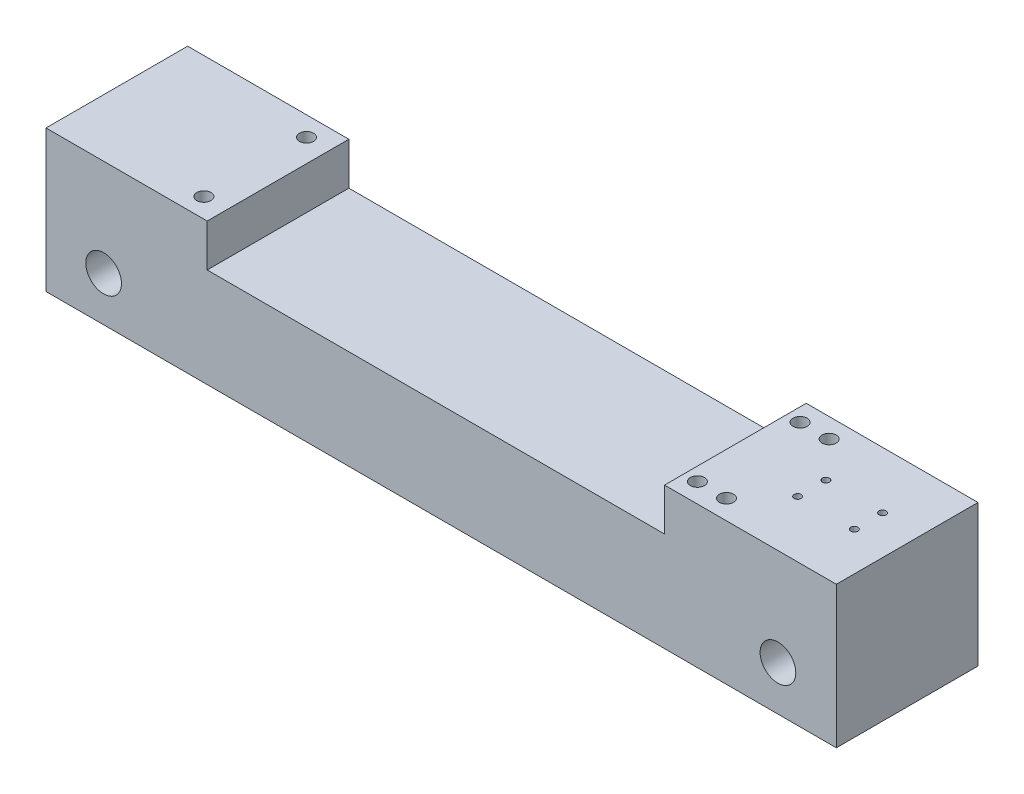
SolidWorks part; units mm, degrees
material "6061 Alloy"
ref_plane "Front Plane" through (0, 0, 0) normal (0, 0, 1) x (1, 0, 0)
ref_plane "Top Plane" through (0, 0, 0) normal (0, 1, 0) x (1, 0, 0)
ref_plane "Right Plane" through (0, 0, 0) normal (1, 0, 0) x (0, 0, -1)
sketch "Sketch1" plane through (0, 0, 0) normal (0, 0, 1) x (1, 0, 0)
  line L0 (177.125, 59) -> (177.125, 63.5)
  line L1 (177.125, 63.5) -> (100.125, 63.5)
  line L2 (100.125, 63.5) -> (100.125, 59)
  line L3 (100.125, 44.5) -> (-104.875, 44.5)
  line L4 (-2.375, 44.5) -> (-2.375, 40)
  line L5 (-104.875, 63.5) -> (-177.125, 63.5)
  line L6 (-177.125, 63.5) -> (-177.125, 59)
  line L7 (-104.875, 63.5) -> (-104.875, 59)
  circle A0 centre (164.385, 33.435) radius 2.6035
  circle A1 centre (169.95, 20) radius 2.6035
  circle A2 centre (164.385, 6.565) radius 2.6035
  circle A3 centre (137.515, 6.565) radius 2.6035
  circle A4 centre (131.95, 20) radius 2.6035
  circle A5 centre (137.515, 33.435) radius 2.6035
  circle A6 centre (-137.865, 33.435) radius 2.6035
  circle A7 centre (-132.3, 20) radius 2.6035
  circle A8 centre (-137.865, 6.565) radius 2.6035
  circle A9 centre (-164.735, 6.565) radius 2.6035
  circle A10 centre (-170.3, 20) radius 2.6035
  circle A11 centre (-164.735, 33.435) radius 2.6035
  point P37 (-182.0987, 63.5)
  line B0 (-177.125, 0) -> (177.125, 0)
  line B1 (177.125, 0) -> (177.125, 59)
  line B2 (177.125, 59) -> (100.125, 59)
  line B3 (100.125, 59) -> (100.125, 40)
  line B4 (100.125, 40) -> (-104.875, 40)
  line B5 (-104.875, 40) -> (-104.875, 59)
  line B6 (-104.875, 59) -> (-177.125, 59)
  line B7 (-177.125, 59) -> (-177.125, 0)
  circle B8 centre (-151.3, 20) radius 14
  circle B9 centre (150.95, 20) radius 14
  arc B10 (-164.735, 9.315) -> (-164.735, 3.815) centre (-164.735, 6.565) ccw
  arc B11 (-164.735, 9.315) -> (-164.735, 3.815) centre (-164.735, 6.565) ccw
  arc B12 (-164.735, 3.815) -> (-164.735, 9.315) centre (-164.735, 6.565) ccw
  arc B13 (-164.735, 3.815) -> (-164.735, 9.315) centre (-164.735, 6.565) ccw
  arc B14 (-137.865, 3.815) -> (-137.865, 9.315) centre (-137.865, 6.565) ccw
  arc B15 (-137.865, 3.815) -> (-137.865, 9.315) centre (-137.865, 6.565) ccw
  arc B16 (-137.865, 9.315) -> (-137.865, 3.815) centre (-137.865, 6.565) ccw
  arc B17 (-137.865, 9.315) -> (-137.865, 3.815) centre (-137.865, 6.565) ccw
  arc B18 (-132.3, 17.25) -> (-132.3, 22.75) centre (-132.3, 20) ccw
  arc B19 (-132.3, 17.25) -> (-132.3, 22.75) centre (-132.3, 20) ccw
  arc B20 (-132.3, 22.75) -> (-132.3, 17.25) centre (-132.3, 20) ccw
  arc B21 (-132.3, 22.75) -> (-132.3, 17.25) centre (-132.3, 20) ccw
  arc B22 (-137.865, 30.685) -> (-137.865, 36.185) centre (-137.865, 33.435) ccw
  arc B23 (-137.865, 30.685) -> (-137.865, 36.185) centre (-137.865, 33.435) ccw
  arc B24 (-137.865, 36.185) -> (-137.865, 30.685) centre (-137.865, 33.435) ccw
  arc B25 (-137.865, 36.185) -> (-137.865, 30.685) centre (-137.865, 33.435) ccw
  arc B26 (-170.3, 17.25) -> (-170.3, 22.75) centre (-170.3, 20) ccw
  arc B27 (-170.3, 17.25) -> (-170.3, 22.75) centre (-170.3, 20) ccw
  arc B28 (-170.3, 22.75) -> (-170.3, 17.25) centre (-170.3, 20) ccw
  arc B29 (-170.3, 22.75) -> (-170.3, 17.25) centre (-170.3, 20) ccw
  arc B30 (-164.735, 30.685) -> (-164.735, 36.185) centre (-164.735, 33.435) ccw
  arc B31 (-164.735, 30.685) -> (-164.735, 36.185) centre (-164.735, 33.435) ccw
  arc B32 (-164.735, 36.185) -> (-164.735, 30.685) centre (-164.735, 33.435) ccw
  arc B33 (-164.735, 36.185) -> (-164.735, 30.685) centre (-164.735, 33.435) ccw
  arc B34 (137.515, 9.315) -> (137.515, 3.815) centre (137.515, 6.565) ccw
  arc B35 (137.515, 9.315) -> (137.515, 3.815) centre (137.515, 6.565) ccw
  arc B36 (137.515, 3.815) -> (137.515, 9.315) centre (137.515, 6.565) ccw
  arc B37 (137.515, 3.815) -> (137.515, 9.315) centre (137.515, 6.565) ccw
  arc B38 (164.385, 9.315) -> (164.385, 3.815) centre (164.385, 6.565) ccw
  arc B39 (164.385, 9.315) -> (164.385, 3.815) centre (164.385, 6.565) ccw
  arc B40 (164.385, 3.815) -> (164.385, 9.315) centre (164.385, 6.565) ccw
  arc B41 (164.385, 3.815) -> (164.385, 9.315) centre (164.385, 6.565) ccw
  arc B42 (169.95, 17.25) -> (169.95, 22.75) centre (169.95, 20) ccw
  arc B43 (169.95, 17.25) -> (169.95, 22.75) centre (169.95, 20) ccw
  arc B44 (169.95, 22.75) -> (169.95, 17.25) centre (169.95, 20) ccw
  arc B45 (169.95, 22.75) -> (169.95, 17.25) centre (169.95, 20) ccw
  arc B46 (164.385, 30.685) -> (164.385, 36.185) centre (164.385, 33.435) ccw
  arc B47 (164.385, 30.685) -> (164.385, 36.185) centre (164.385, 33.435) ccw
  arc B48 (164.385, 36.185) -> (164.385, 30.685) centre (164.385, 33.435) ccw
  arc B49 (164.385, 36.185) -> (164.385, 30.685) centre (164.385, 33.435) ccw
  arc B50 (131.95, 17.25) -> (131.95, 22.75) centre (131.95, 20) ccw
  arc B51 (131.95, 17.25) -> (131.95, 22.75) centre (131.95, 20) ccw
  arc B52 (131.95, 22.75) -> (131.95, 17.25) centre (131.95, 20) ccw
  arc B53 (131.95, 22.75) -> (131.95, 17.25) centre (131.95, 20) ccw
  arc B54 (137.515, 30.685) -> (137.515, 36.185) centre (137.515, 33.435) ccw
  arc B55 (137.515, 30.685) -> (137.515, 36.185) centre (137.515, 33.435) ccw
  arc B56 (137.515, 36.185) -> (137.515, 30.685) centre (137.515, 33.435) ccw
  arc B57 (137.515, 36.185) -> (137.515, 30.685) centre (137.515, 33.435) ccw
  dimension "D1" = 5.207
  dimension "D2" = 63.5
sketch_block_instance "Block-SecondaryBlock Sideview-1"
sketch_block "Block-SecondaryBlock Sideview"
extrude "Boss-Extrude1" add sketch "Sketch1" along normal blind 63.5 contours B6 B7 B0 B1 B2 B3 B4 B5 B56 B54 B52 B50 B48 B46 B44 B42 B40 B38 B36 B34 B32 B30 B28 B26 B24 B22 B20 B18 B16 B14 B12 B10 B9 B8 | B46 B48 A0 | B54 B56 A5 | B42 B44 A1 | B38 B40 A2 | B50 B52 A4 | B34 B36 A3 | B22 B24 A6 | B18 B20 A7 | B14 B16 A8 | B10 B12 A9 | B26 B28 A10 | B30 B32 A11 | B2 L0 L1 L2 | B4 B3 L3 L4 | B6 L7 L5 L6 | B5 B4 L4 L3 region at (138.625, 61.25, 0) region at (0.6144, 25.4009, 0) region at (48.875, 42.25, 0) region at (-141, 61.25, 0) region at (-53.625, 42.25, 0) region at (-162.0628, 6.565, 0) region at (-140.5372, 6.565, 0) region at (-134.9722, 20, 0) region at (-140.5372, 33.435, 0) region at (-172.9722, 20, 0) region at (-167.4072, 33.435, 0) region at (140.1872, 6.565, 0) region at (167.0572, 6.565, 0) region at (167.2778, 20, 0) region at (161.7128, 33.435, 0) region at (129.2778, 20, 0) region at (134.8428, 33.435, 0)
sketch "Sketch2" plane through (0, 63.5, 0) normal (0, 1, 0) x (1, 0, 0)
  line L0 (177.125, -61.75) -> (177.125, -1.75)
  line L2 (177.125, -63.5) -> (177.125, 0) construction
  circle A0 centre (119.125, -54.75) radius 3.175
  circle A1 centre (106.125, -54.75) radius 3.175
  circle A2 centre (119.125, -8.75) radius 3.175
  circle A3 centre (106.125, -8.75) radius 3.175
  circle A4 centre (-115.125, -54.75) radius 3.175
  circle A5 centre (-115.125, -8.75) radius 3.175
  point P13 (177.125, -31.75)
  point P20 (177.125, -31.75)
  line B0 (-177.125, -1.75) -> (177.125, -1.75)
  line B1 (177.125, -1.75) -> (177.125, -41.55)
  line B2 (177.125, -41.55) -> (-177.125, -41.55) construction
  line B3 (-177.125, -41.55) -> (-177.125, -1.75)
  line B4 (-177.125, -41.55) -> (-177.125, -61.75)
  line B5 (-177.125, -61.75) -> (177.125, -61.75)
  line B6 (177.125, -61.75) -> (177.125, -41.55)
  arc B7 (-118.425, -8.75) -> (-111.825, -8.75) centre (-115.125, -8.75) ccw
  arc B8 (-111.825, -8.75) -> (-118.425, -8.75) centre (-115.125, -8.75) ccw
  arc B9 (-118.425, -54.75) -> (-111.825, -54.75) centre (-115.125, -54.75) ccw
  arc B10 (-111.825, -54.75) -> (-118.425, -54.75) centre (-115.125, -54.75) ccw
  arc B11 (-132.725, -34.65) -> (-128.525, -34.65) centre (-130.625, -34.65) ccw
  arc B12 (-128.525, -34.65) -> (-132.725, -34.65) centre (-130.625, -34.65) ccw
  arc B13 (-132.725, -8.65) -> (-128.525, -8.65) centre (-130.625, -8.65) ccw
  arc B14 (-128.525, -8.65) -> (-132.725, -8.65) centre (-130.625, -8.65) ccw
  arc B15 (-173.725, -34.65) -> (-169.525, -34.65) centre (-171.625, -34.65) ccw
  arc B16 (-169.525, -34.65) -> (-173.725, -34.65) centre (-171.625, -34.65) ccw
  arc B17 (-173.725, -8.65) -> (-169.525, -8.65) centre (-171.625, -8.65) ccw
  arc B18 (-169.525, -8.65) -> (-173.725, -8.65) centre (-171.625, -8.65) ccw
  arc B19 (128.525, -8.65) -> (132.725, -8.65) centre (130.625, -8.65) ccw
  arc B20 (132.725, -8.65) -> (128.525, -8.65) centre (130.625, -8.65) ccw
  arc B21 (169.525, -8.65) -> (173.725, -8.65) centre (171.625, -8.65) ccw
  arc B22 (173.725, -8.65) -> (169.525, -8.65) centre (171.625, -8.65) ccw
  arc B23 (169.525, -34.65) -> (173.725, -34.65) centre (171.625, -34.65) ccw
  arc B24 (173.725, -34.65) -> (169.525, -34.65) centre (171.625, -34.65) ccw
  arc B25 (128.525, -34.65) -> (132.725, -34.65) centre (130.625, -34.65) ccw
  arc B26 (132.725, -34.65) -> (128.525, -34.65) centre (130.625, -34.65) ccw
  arc B27 (115.825, -54.75) -> (122.425, -54.75) centre (119.125, -54.75) ccw
  arc B28 (122.425, -54.75) -> (115.825, -54.75) centre (119.125, -54.75) ccw
  arc B29 (102.825, -54.75) -> (109.425, -54.75) centre (106.125, -54.75) ccw
  arc B30 (109.425, -54.75) -> (102.825, -54.75) centre (106.125, -54.75) ccw
  arc B31 (115.825, -8.75) -> (122.425, -8.75) centre (119.125, -8.75) ccw
  arc B32 (122.425, -8.75) -> (115.825, -8.75) centre (119.125, -8.75) ccw
  arc B33 (102.825, -8.75) -> (109.425, -8.75) centre (106.125, -8.75) ccw
  arc B34 (109.425, -8.75) -> (102.825, -8.75) centre (106.125, -8.75) ccw
  dimension "D1" = 6.35
sketch_block_instance "Block-SecondaryBlock Topview-1"
sketch_block "Block-SecondaryBlock Topview"
extrude "Cut-Extrude1" cut sketch "Sketch2" against normal blind 19.05 contours A0 | A1 | A2 | A3 | A4 | A5 region at (119.125, 63.5, 54.75) region at (106.125, 63.5, 54.75) region at (119.125, 63.5, 8.75) region at (106.125, 63.5, 8.75) region at (-115.125, 63.5, 54.75) region at (-115.125, 63.5, 8.75)
extrude "Cut-Extrude3" cut sketch "Sketch2<3>" along normal blind 12.7 from surface contours B23 B24 | B25 B26 | B19 B20 | B21 B22 | B11 B12 | B13 B14 | B17 B18 | B15 B16 region at (-130.625, 63.5, 34.65) region at (-130.625, 63.5, 8.65) region at (-171.625, 63.5, 34.65) region at (-171.625, 63.5, 8.65) region at (130.625, 63.5, 8.65) region at (171.625, 63.5, 8.65) region at (171.625, 63.5, 34.65) region at (130.625, 63.5, 34.65) starting at face at (0, 0, 31.75)
sketch "Sketch2<3>" plane through (0, 63.5, 0) normal (0, 1, 0) x (1, 0, 0) same geometry as "Sketch2"
sketch "Sketch3" plane through (0, 0, 0) normal (0, 0, -1) x (-1, 0, 0)
  circle A1 centre (-150.95, 20) radius 8
  circle A3 centre (-150.95, 20) radius 14
  circle A4 centre (-150.95, 20) radius 14 construction
  circle A5 centre (151.3, 20) radius 8
  circle A6 centre (151.3, 20) radius 14
  circle A7 centre (151.3, 20) radius 14 construction
  dimension "D2" = 16
extrude "Boss-Extrude2" add sketch "Sketch3" along normal offset from surface (31.5 mm away) 32 from surface up to face at (164.95, 20, 0) starting at face at (164.95, 20, 63.5)
sketch "Sketch4" plane through (0, 63.5, 0) normal (0, 1, 0) x (1, 0, 0)
  line L0 (177.125, -63.5) -> (177.125, 0) construction
  point P0 (161.9871, -18.3109)
  point P1 (100.125, -31.75)
  point P5 (177.125, -31.75)
  line B0 (177.125, -1.75) -> (100.125, -1.75)
  line B1 (100.125, -1.75) -> (100.125, -61.75)
  line B2 (100.125, -61.75) -> (177.125, -61.75)
  line B3 (177.125, -61.75) -> (177.125, -1.75)
  line B4 (128.025, -22.25) -> (128.025, -41.25) construction
  line B5 (128.025, -22.25) -> (166.125, -22.25) construction
  line B6 (128.025, -41.25) -> (166.125, -41.25) construction
  line B7 (166.125, -22.25) -> (166.125, -41.25) construction
  circle B8 centre (134.375, -38.075) radius 1.5875
  circle B9 centre (134.375, -25.425) radius 1.5875
  circle B10 centre (159.775, -25.425) radius 1.5875
  circle B11 centre (159.775, -38.075) radius 1.5875
sketch_block_instance "Block-MotorMounting TopView 2-1"
sketch_block "Block-MotorMounting TopView 2"
extrude "Cut-Extrude4" cut sketch "Sketch4" against normal blind 6.35 contours B11 | B10 | B9 | B8 region at (134.375, 63.5, 38.075) region at (134.375, 63.5, 25.425) region at (159.775, 63.5, 25.425) region at (159.775, 63.5, 38.075)
sketch "Sketch5" plane through (0, 0, 63.5) normal (0, 0, 1) x (1, 0, 0)
  circle A0 centre (131.95, 20) radius 2.6035 construction
  circle A1 centre (137.515, 6.565) radius 2.6035 construction
  circle A2 centre (164.385, 6.565) radius 2.6035 construction
  circle A3 centre (169.95, 20) radius 2.6035 construction
  circle A4 centre (164.385, 33.435) radius 2.6035 construction
  circle A5 centre (137.515, 33.435) radius 2.6035 construction
  circle A6 centre (-137.865, 6.565) radius 2.6035 construction
  circle A7 centre (-132.3, 20) radius 2.6035 construction
  circle A8 centre (-137.865, 33.435) radius 2.6035 construction
  circle A9 centre (-164.735, 6.565) radius 2.6035 construction
  circle A10 centre (-170.3, 20) radius 2.6035 construction
  circle A11 centre (-164.735, 33.435) radius 2.6035 construction
  circle A12 centre (131.95, 20) radius 2.6035
  circle A13 centre (137.515, 6.565) radius 2.6035
  circle A14 centre (164.385, 6.565) radius 2.6035
  circle A15 centre (169.95, 20) radius 2.6035
  circle A16 centre (164.385, 33.435) radius 2.6035
  circle A17 centre (137.515, 33.435) radius 2.6035
  circle A18 centre (-137.865, 6.565) radius 2.6035
  circle A19 centre (-132.3, 20) radius 2.6035
  circle A20 centre (-137.865, 33.435) radius 2.6035
  circle A21 centre (-164.735, 6.565) radius 2.6035
  circle A22 centre (-170.3, 20) radius 2.6035
  circle A23 centre (-164.735, 33.435) radius 2.6035
extrude "Boss-Extrude3" add sketch "Sketch5" against normal offset from surface (50.8 mm away) 12.7 up to face at (164.95, 20, 0)
